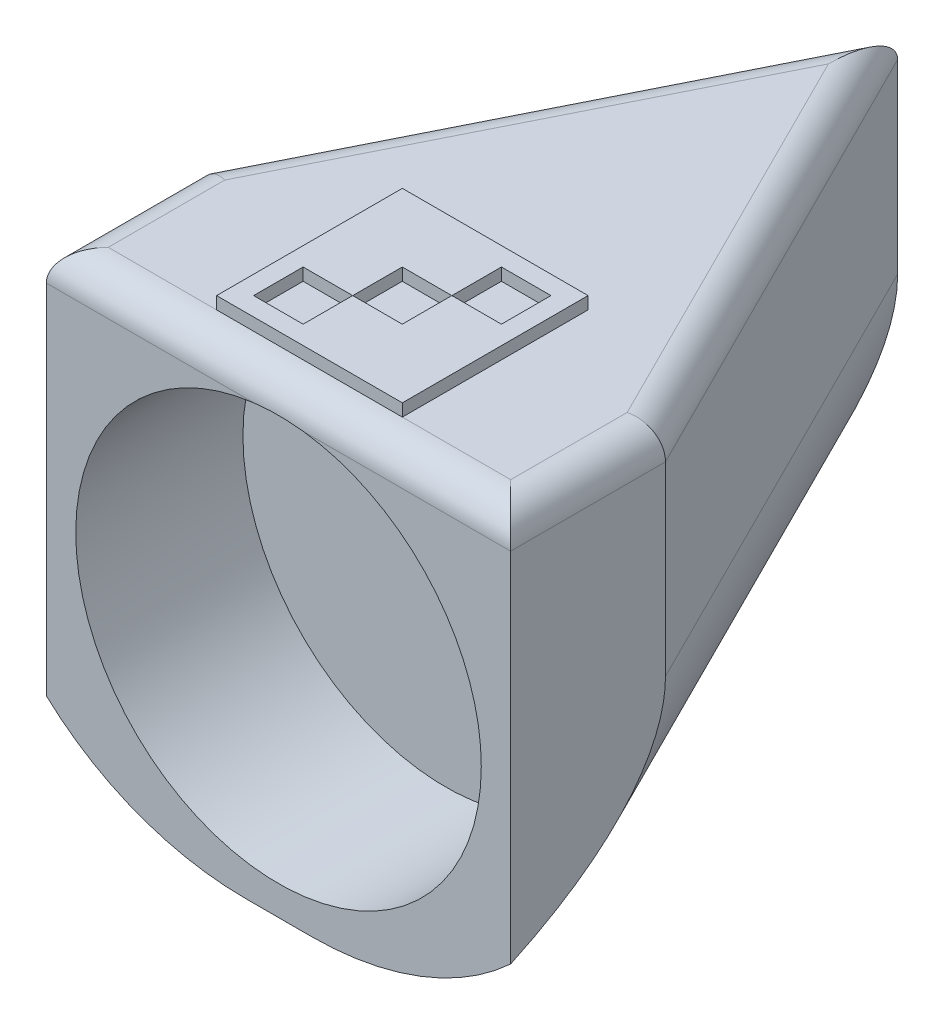
SolidWorks part; units mm, degrees
ref_plane "Alzado" through (0, 0, 0) normal (0, 0, 1) x (1, 0, 0)
ref_plane "Planta" through (0, 0, 0) normal (0, 1, 0) x (1, 0, 0)
ref_plane "Vista lateral" through (0, 0, 0) normal (1, 0, 0) x (0, 0, -1)
sketch "Croquis1" plane through (0, 0, 0) normal (0, 1, 0) x (1, 0, 0)
  line L0 (-37.5, -75) -> (0, 0)
  line L1 (0, 0) -> (37.5, -75)
  line L2 (37.5, -75) -> (-37.5, -75)
  line L3 (0, 35.9139) -> (0, -110.1255) construction
  line L5 (-37.5, -75) -> (37.5, -75)
  line L6 (-37.5, -75) -> (-37.5, -100)
  line L7 (-37.5, -100) -> (37.5, -100)
  line L8 (37.5, -75) -> (37.5, -100)
  point P7 (0, -75)
  dimension "D1" = 75
  dimension "D2" = 75
  dimension "D3" = 25
extrude "Saliente-Extruir1" add sketch "Croquis1" along normal blind 75 contours L3 L0 L5 | L1 L3 L2 | L2 L3 L7 L8 | L3 L5 L6 L7 region at (-12.5, 0, 50) region at (-18.75, 0, 87.5) region at (12.5, 0, 50) region at (18.75, 0, 87.5)
sketch "Croquis3" plane through (0, 0, 100) normal (0, 0, 1) x (1, 0, 0)
  line L0 (-37.5, 75) -> (37.5, 0) construction
  circle A0 centre (0, 37.5) radius 32.75
  dimension "D1" = 65.5
extrude "Cortar-Extruir2" cut sketch "Croquis3" against normal blind 27
fillet "Redondeo4" radius 40 2 edges at (-18.75, 0, 37.5) (18.75, 0, 37.5)
fillet "Redondeo5" radius 5 5 edges at (18.75, 75, 37.5) (-18.75, 75, 37.5) (-37.5, 75, 87.5) (37.5, 75, 87.5) (0, 75, 100)
sketch "Croquis4" plane through (0, 75, 0) normal (0, 1, 0) x (1, 0, 0)
  line L0 (0, 16.0968) -> (0, -119.7518) construction
  line L1 (15, -95) -> (-15, -95)
  line L2 (15, -95) -> (15, -65)
  line L3 (15, -65) -> (-15, -65)
  line L4 (-15, -95) -> (-15, -65)
  line L5 (15, -65) -> (-15, -95) construction
  line L22 (-32.5, -95) -> (32.5, -95) construction
  point P7 (0, -95)
  point P12 (0, 0)
  point P21 (0, 0)
  point P25 (0, 0)
  point P27 (-11.9983, -91.9983)
  point P28 (-15, -65)
  point P29 (-15, -65)
  point P30 (4.0017, -75.9983)
  point P31 (12.0017, -67.9983)
  point P32 (4.0017, -75.9983)
  point P33 (-3.9983, -83.9983)
  point P34 (-3.9983, -75.9983)
  dimension "D1" = 30
  dimension "D2" = 30
extrude "Saliente-Extruir2" add sketch "Croquis4" along normal blind 2 contours L2 L1 L4 L3
sketch "Croquis5" plane through (0, 77, 0) normal (0, 1, 0) x (1, 0, 0)
  line L0 (-15, -95) -> (15, -65) construction
  line L2 (-12.0123, -92.0123) -> (-4.0123, -92.0123)
  line L3 (-12.0123, -92.0123) -> (-12.0123, -84.0123)
  line L4 (-12.0123, -84.0123) -> (-4.0123, -84.0123)
  line L5 (-4.0123, -92.0123) -> (-4.0123, -84.0123)
  line L10 (4.0019, -75.9981) -> (12.0019, -75.9981)
  line L11 (4.0019, -75.9981) -> (4.0019, -67.9981)
  line L12 (4.0019, -67.9981) -> (12.0019, -67.9981)
  line L13 (12.0019, -75.9981) -> (12.0019, -67.9981)
  line L14 (-4.0052, -84.0052) -> (3.9948, -84.0052)
  line L15 (-4.0052, -84.0052) -> (-4.0052, -76.0052)
  line L16 (-4.0052, -76.0052) -> (3.9948, -76.0052)
  line L17 (3.9948, -84.0052) -> (3.9948, -76.0052)
  point P12 (0, 0)
  point P17 (0, 0)
  dimension "D1" = 8
  dimension "D2" = 0.01
  dimension "D3" = 8
  dimension "D4" = 4.24
  dimension "D5" = 4.2253
  dimension "D6" = 0.01
  dimension "D7" = 8
extrude "Cortar-Extruir10" cut sketch "Croquis5" against normal blind 2 contours L3 L2 L5 L4 | L15 L14 L17 L16 | L11 L10 L13 L12
